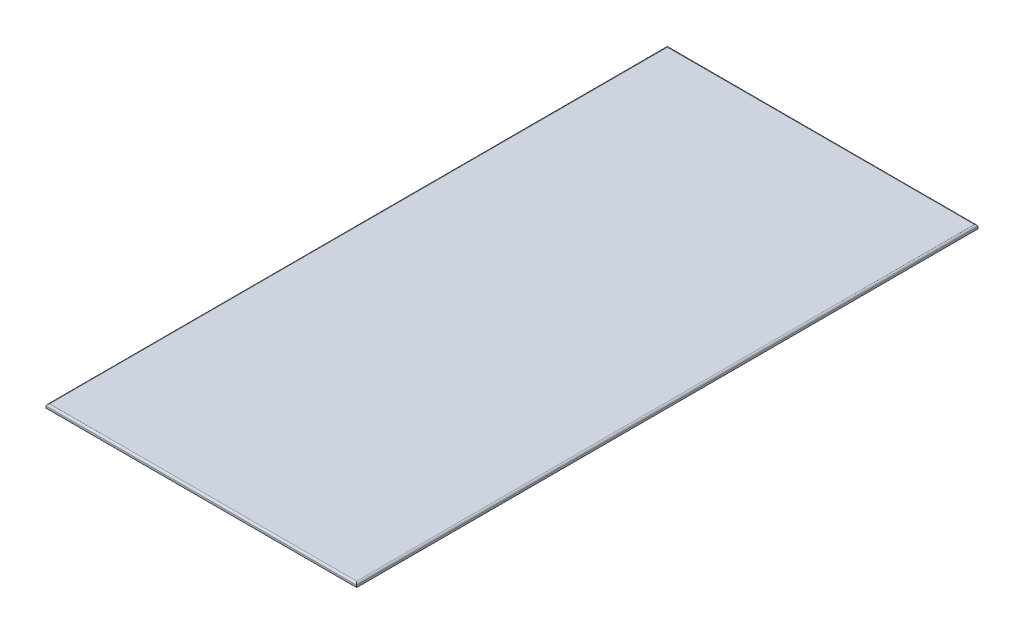
SolidWorks part; units mm, degrees
ref_plane "Front Plane" through (0, 0, 0) normal (0, 0, 1) x (1, 0, 0)
ref_plane "Top Plane" through (0, 0, 0) normal (0, 1, 0) x (1, 0, 0)
ref_plane "Right Plane" through (0, 0, 0) normal (1, 0, 0) x (0, 0, -1)
sketch "Sketch1" plane through (0, 0, 0) normal (0, 1, 0) x (1, 0, 0)
  line L1 (0, 0) -> (500, 0)
  line L2 (0, 0) -> (0, 1000)
  line L3 (0, 1000) -> (500, 1000)
  line L4 (500, 0) -> (500, 1000)
  dimension "D1" = 500
  dimension "D2" = 1000
extrude "Boss-Extrude1" add sketch "Sketch1" along normal blind 6
fillet "Fillet1" radius 3 4 edges at (250, 6, -1000) (500, 6, -500) (250, 6, 0) (0, 6, -500)
sketch "Sketch2" plane through (0, 6, 0) normal (0, 1, 0) x (1, 0, 0)
  line L1 (419.6467, 433.6686) -> (460.7512, 433.6686)
  line L2 (419.6467, 433.6686) -> (419.6467, 300.1493)
  line L3 (419.6467, 300.1493) -> (460.7512, 300.1493)
  line L4 (460.7512, 433.6686) -> (460.7512, 300.1493)
  circle A0 centre (130.0893, 351.7931) radius 75
  circle A1 centre (316.2468, 351.7931) radius 50
  circle A2 centre (130.0893, 143.7401) radius 75
  circle A3 centre (364.3301, 143.7401) radius 100
  circle A4 centre (364.3301, 143.7401) radius 65
  circle A5 centre (449.544, 420.752) radius 5.3994
  circle A6 centre (429.544, 420.752) radius 5.3994
  circle A7 centre (429.544, 400.752) radius 5.3994
  circle A8 centre (429.544, 380.752) radius 5.3994
  circle A9 centre (429.544, 360.752) radius 5.3994
  circle A10 centre (449.544, 400.752) radius 5.3994
  circle A11 centre (449.544, 380.752) radius 5.3994
  circle A12 centre (449.544, 360.752) radius 5.3994
  dimension "D1" = 150
  dimension "D2" = 150
  dimension "D3" = 200
  dimension "D4" = 130
  dimension "D5" = 100
  dimension "D6" = 2
  dimension "D7" = 4
sketch "Sketch3" plane through (0, 0, 0) normal (0, -1, 0) x (1, 0, 0)
  line L0 (450, -50) -> (50, -50)
  line L1 (50, -50) -> (50, -950)
  line L2 (50, -950) -> (450, -950)
  line L3 (450, -950) -> (450, -50)
  line L4 (0, 0) -> (0, -1000)
  line L5 (0, -1000) -> (500, -1000)
  line L6 (500, -1000) -> (500, 0)
  line L7 (500, 0) -> (0, 0)
  line L8 (0, 0) -> (0, -1000)
  line L9 (0, -1000) -> (500, -1000)
  line L10 (500, -1000) -> (500, 0)
  line L11 (500, 0) -> (0, 0)
  dimension "D1" = 0
  dimension "D2" = 50
extrude "Boss-Extrude2" add sketch "Sketch3" along normal blind 26 contours L2 L3 L0 L1 region at (250, 0, -500)
fillet "Fillet2" radius 6 8 edges at (50, -26, -500) (250, -26, -50) (450, -26, -500) (250, -26, -950) (50, -13, -50) (50, -13, -950) (450, -13, -950) (450, -13, -50)
